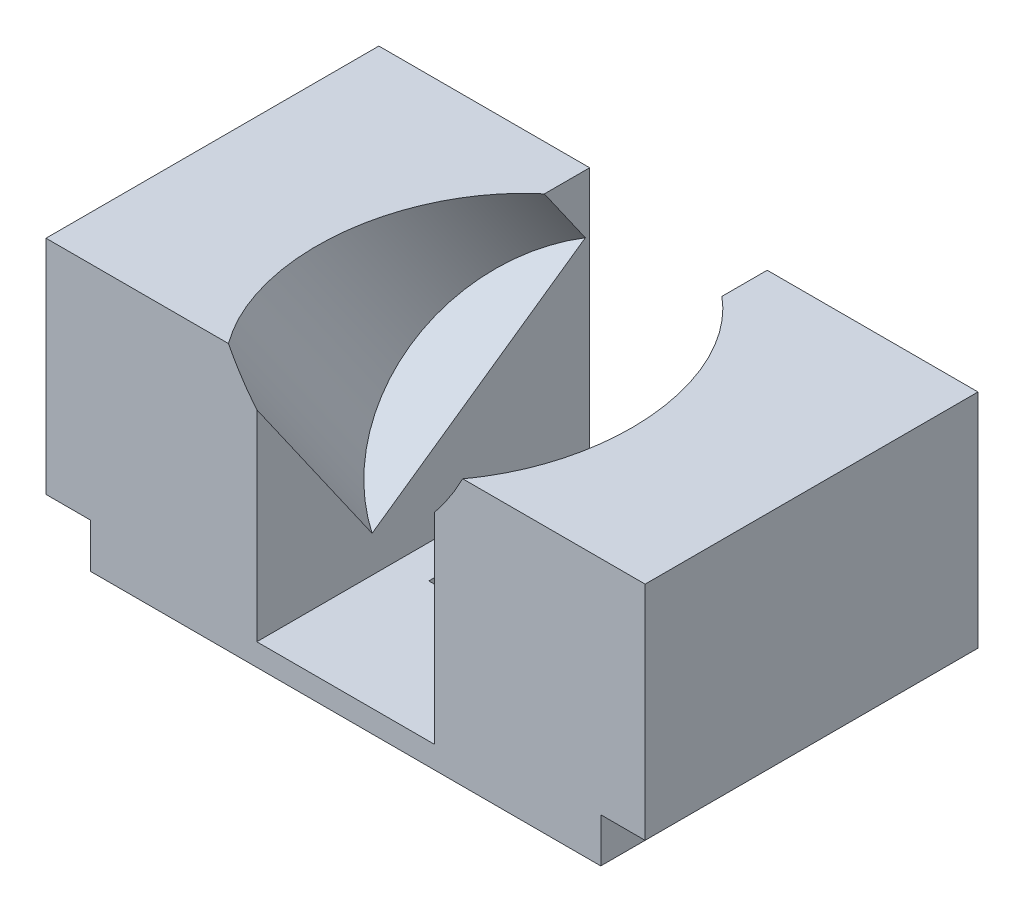
SolidWorks part; units mm, degrees
ref_plane "Front Plane" through (0, 0, 0) normal (0, 0, 1) x (1, 0, 0)
ref_plane "Top Plane" through (0, 0, 0) normal (0, 1, 0) x (1, 0, 0)
ref_plane "Right Plane" through (0, 0, 0) normal (1, 0, 0) x (0, 0, -1)
sketch "Sketch1" plane through (0, 0, 0) normal (1, 0, 0) x (0, 0, -1)
  line L1 (-25.4, 15.24) -> (25.4, 15.24)
  line L2 (-25.4, 15.24) -> (-25.4, -15.24)
  line L3 (-25.4, -15.24) -> (25.4, -15.24)
  line L4 (25.4, 15.24) -> (25.4, -15.24)
  line L5 (-25.4, 15.24) -> (25.4, -15.24) construction
  line L6 (-25.4, -15.24) -> (25.4, 15.24) construction
  point P0 (0, 0)
  dimension "D1" = 30.48
  dimension "D2" = 50.8
extrude "Boss-Extrude1" add sketch "Sketch1" along normal mid plane 68.58
ref_axis "Axis1" through (-37.719, 0, 0) along (1, 0, 0)
ref_plane "Plane1" through (0, 0, 0) normal (0, 0.8192, 0.5736) x (1, 0, 0)
sketch "Sketch2" plane through (0, 0, 0) normal (0, 0.8192, 0.5736) x (1, 0, 0)
  circle A0 centre (0, 0) radius 18.034
  dimension "D1" = 36.068
extrude "Cut-Extrude1" cut sketch "Sketch2" along normal through all
sketch "Sketch3" plane through (0, 0, 25.4) normal (0, 0, 1) x (1, 0, 0)
  line L1 (-10.16, -12.7) -> (10.16, -12.7)
  line L2 (-10.16, -12.7) -> (-10.16, 15.24)
  line L3 (-10.16, 15.24) -> (10.16, 15.24)
  line L4 (10.16, -12.7) -> (10.16, 15.24)
  line L5 (18.034, 15.24) -> (-18.034, 15.24) construction
  line L6 (34.29, -15.24) -> (-34.29, -15.24) construction
  point P8 (0, 15.24)
  dimension "D1" = 2.54
  dimension "D2" = 20.32
extrude "Cut-Extrude2" cut sketch "Sketch3" against normal through all
sketch "Sketch4" plane through (0, 0, 0) normal (0, 1, 0) x (1, 0, 0)
  line L1 (6.35, 9.525) -> (-6.35, 9.525)
  line L2 (6.35, 9.525) -> (6.35, -9.525)
  line L3 (6.35, -9.525) -> (-6.35, -9.525)
  line L4 (-6.35, 9.525) -> (-6.35, -9.525)
  line L5 (6.35, 9.525) -> (-6.35, -9.525) construction
  line L6 (6.35, -9.525) -> (-6.35, 9.525) construction
  point P0 (0, 0)
  dimension "D1" = 19.05
  dimension "D2" = 12.7
extrude "Cut-Extrude3" cut sketch "Sketch4" against normal through all
sketch "Sketch7" plane through (0, 15.24, 0) normal (0, 1, 0) x (1, 0, 0)
  line L0 (34.29, 25.4) -> (34.29, -25.4) construction
  line L1 (-34.29, 25.4) -> (34.29, 25.4)
  line L2 (-34.29, 25.4) -> (-34.29, 12.7)
  line L3 (-34.29, 12.7) -> (34.29, 12.7)
  line L4 (34.29, 25.4) -> (34.29, 12.7)
  dimension "D1" = 12.7
extrude "Cut-Extrude5" cut sketch "Sketch7" against normal through all
sketch "Sketch9" plane through (0, 0, 0) normal (0, 0, 1) x (1, 0, 0)
  line L0 (0, 0) -> (0, -6.0325) construction
  line L1 (-34.29, -15.24) -> (-29.21, -15.24)
  line L2 (-34.29, -15.24) -> (-34.29, -10.16)
  line L3 (-34.29, -10.16) -> (-29.21, -10.16)
  line L4 (-29.21, -15.24) -> (-29.21, -10.16)
  line L5 (29.21, -15.24) -> (29.21, -10.16)
  line L6 (34.29, -10.16) -> (29.21, -10.16)
  line L7 (34.29, -15.24) -> (34.29, -10.16)
  line L8 (34.29, -15.24) -> (29.21, -15.24)
  dimension "D1" = 5.08
extrude "Cut-Extrude6" cut sketch "Sketch9" against normal through all both and the other way through all
